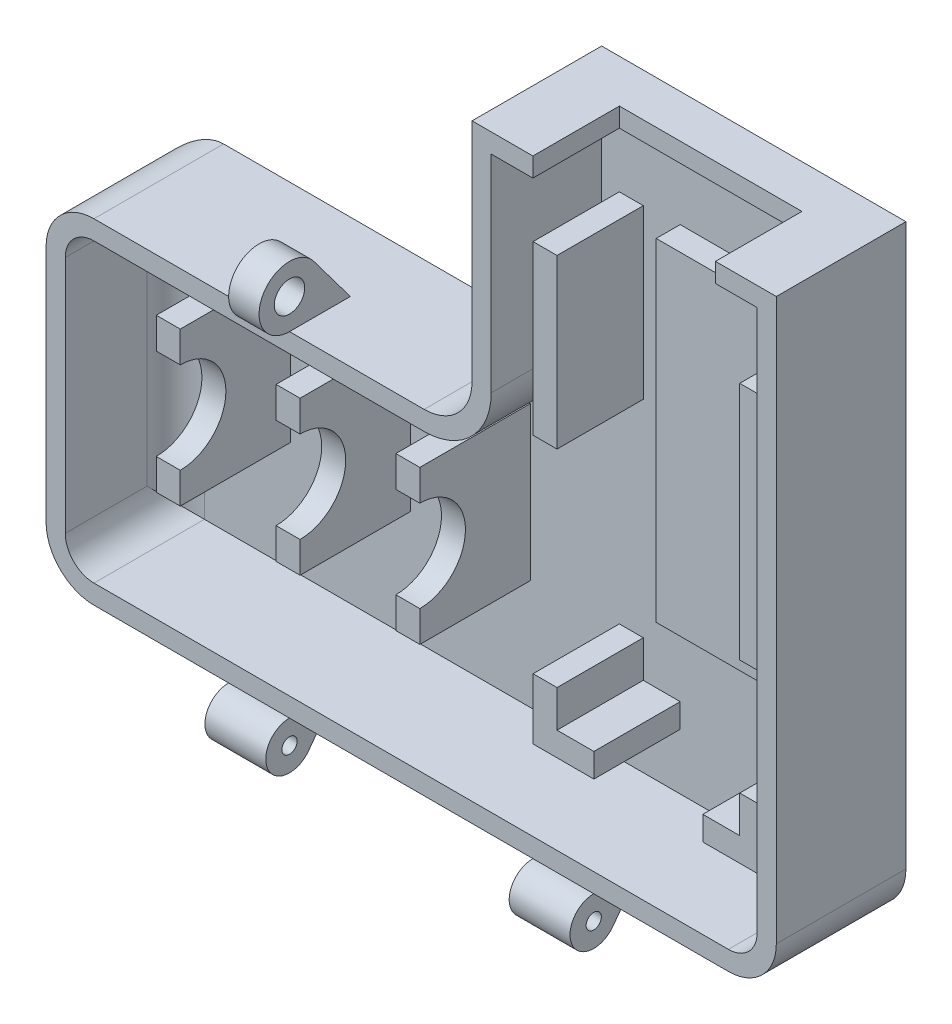
SolidWorks part; units mm, degrees
material "PET"
ref_plane "Alzado" through (0, 0, 0) normal (0, 0, 1) x (1, 0, 0)
ref_plane "Planta" through (0, 0, 0) normal (0, 1, 0) x (1, 0, 0)
ref_plane "Vista lateral" through (0, 0, 0) normal (1, 0, 0) x (0, 0, -1)
sketch "Croquis1" plane through (0, 0, 0) normal (0, 0, 1) x (1, 0, 0)
  line L0 (0, 0) -> (0, 127)
  line L1 (0, 127) -> (63.5, 127)
  line L2 (63.5, 69.85) -> (152.4, 69.85)
  line L3 (152.4, 0) -> (0, 0)
  line L4 (63.5, 69.85) -> (63.5, 127)
  line L5 (152.4, 69.85) -> (152.4, 0)
  dimension "D1" = 63.5
  dimension "D2" = 152.4
  dimension "D3" = 127
  dimension "D4" = 57.15
extrude "Saliente-Extruir1" add sketch "Croquis1" along normal blind 54.1
fillet "Redondeo1" radius 10 5 edges at (152.4, 34.925, 0) (0, 0, 27.05) (152.4, 0, 27.05) (152.4, 69.85, 27.05) (63.5, 69.85, 27.05)
sketch "Croquis2" plane through (152.4, 0, 0) normal (1, 0, 0) x (0, 0, -1)
  line L0 (0, 0) -> (-54.1, 0) construction
  line L1 (-54.1, 127) -> (-27.05, 127)
  line L2 (-54.1, 127) -> (-54.1, 0)
  line L3 (-54.1, 0) -> (-27.05, 0)
  line L4 (-27.05, 127) -> (-27.05, 0)
extrude "Cortar-Extruir1" cut sketch "Croquis2" against normal through all
shell "Vaciado1" thickness 4 removed face at (80.01, 54.9258, 27.05)
sketch "Croquis3" plane through (0, 0, 4) normal (0, 0, 1) x (1, 0, 0)
  line L0 (12.6847, 20.6881) -> (50.8153, 20.6881)
  line L1 (50.8153, 20.6881) -> (50.8153, 33.3881)
  line L2 (50.8153, 33.3881) -> (139.7153, 33.3881)
  line L3 (139.7153, 33.3881) -> (139.7153, 52.4381)
  line L4 (139.7153, 52.4381) -> (50.8153, 52.4381)
  line L5 (50.8153, 52.4381) -> (50.8153, 122.2881)
  line L6 (50.8153, 122.2881) -> (12.6847, 122.2881)
  line L7 (12.6847, 122.2881) -> (12.6847, 20.6881)
  line L8 (12.6847, 28.3881) -> (7.6847, 28.3881)
  line L9 (7.6847, 28.3881) -> (7.6847, 15.6881)
  line L10 (7.6847, 15.6881) -> (20.3847, 15.6881)
  line L11 (20.3847, 15.6881) -> (20.3847, 20.6881)
  line L12 (50.8153, 28.3881) -> (55.8153, 28.3881)
  line L13 (55.8153, 28.3881) -> (55.8153, 15.6881)
  line L14 (55.8153, 15.6881) -> (43.1153, 15.6881)
  line L15 (43.1153, 15.6881) -> (43.1153, 20.6881)
  line L16 (7.6847, 52.4381) -> (12.6847, 52.4381)
  line L17 (7.6847, 52.4381) -> (7.6847, 102.4381)
  line L18 (7.6847, 102.4381) -> (12.6847, 102.4381)
  line L19 (12.6847, 52.4381) -> (12.6847, 102.4381)
  line L20 (50.8153, 106.4881) -> (55.8153, 106.4881)
  line L21 (50.8153, 106.4881) -> (50.8153, 71.4881)
  line L22 (50.8153, 71.4881) -> (55.8153, 71.4881)
  line L23 (55.8153, 106.4881) -> (55.8153, 71.4881)
  line L24 (20.3847, 106.9132) -> (43.1153, 106.9132)
  line L25 (20.3847, 106.9132) -> (20.3847, 37.5203)
  line L26 (20.3847, 37.5203) -> (43.1153, 37.5203)
  line L27 (43.1153, 106.9132) -> (43.1153, 37.5203)
  line L28 (4, 123) -> (59.5, 123) construction
  point P30 (31.75, 122.2881)
  point P33 (31.75, 123)
  point P34 (31.75, 106.9132)
  dimension "D1" = 101.6
  dimension "D2" = 12.7
  dimension "D3" = 12.7
  dimension "D4" = 5
  dimension "D5" = 5
  dimension "D6" = 5
  dimension "D7" = 50
  dimension "D8" = 35
  dimension "D9" = 38.1306
extrude "Saliente-Extruir2" add sketch "Croquis3" along normal blind 5 contours L27 L24 L25 L26 region at (31.75, 72.2168, 4)
extrude "Saliente-Extruir3" add sketch "Croquis3<3>" along normal blind 18 contours L18 L17 L16 L7 | L23 L20 L5 L22 | L15 L14 L13 L12 L1 L0 | L10 L11 L0 L7 L8 L9 region at (12.5815, 20.5849, 4) region at (50.9185, 20.5849, 4) region at (10.1847, 77.4381, 4) region at (53.3153, 88.9881, 4)
sketch "Croquis3<3>" plane through (0, 0, 4) normal (0, 0, 1) x (1, 0, 0) same geometry as "Croquis3"
sketch "Croquis4" plane through (0, 0, 4) normal (0, 0, 1) x (1, 0, 0)
  line L0 (139.7153, 33.3881) -> (139.7153, 52.4381) construction
  line L1 (74.4, 58.9132) -> (79.4, 58.9132)
  line L2 (74.4, 58.9132) -> (74.4, 26.9131)
  line L3 (74.4, 26.9131) -> (79.4, 26.9131)
  line L4 (79.4, 58.9132) -> (79.4, 26.9131)
  line L5 (99.4, 58.9132) -> (104.4, 58.9132)
  line L6 (99.4, 58.9132) -> (99.4, 26.9131)
  line L7 (99.4, 26.9131) -> (104.4, 26.9131)
  line L8 (104.4, 58.9132) -> (104.4, 26.9131)
  line L9 (124.4, 58.9132) -> (129.4, 58.9132)
  line L10 (124.4, 58.9132) -> (124.4, 26.9131)
  line L11 (124.4, 26.9131) -> (129.4, 26.9131)
  line L12 (129.4, 58.9132) -> (129.4, 26.9131)
  line L13 (152.4, 10) -> (152.4, 59.85) construction
  point P12 (129.4, 42.9131)
  point P15 (139.7153, 42.9131)
  point P16 (104.4, 42.9131)
  point P17 (79.4, 42.9131)
  dimension "D1" = 5
  dimension "D2" = 23
  dimension "D3" = 20
  dimension "D4" = 20
  dimension "D5" = 32.0001
extrude "Saliente-Extruir4" add sketch "Croquis4" along normal up to surface (23.05 mm away) up to face at (80.01, 54.9258, 27.05)
sketch "Croquis5" plane through (129.4, 0, 0) normal (1, 0, 0) x (0, 0, -1)
  line L0 (-27.05, 58.9132) -> (-27.05, 26.9131) construction
  circle A0 centre (-27.05, 42.9131) radius 9.525
  dimension "D1" = 19.05
extrude "Cortar-Extruir2" cut sketch "Croquis5" against normal up to surface (73.5847 mm away) up to face at (55.8153, 22.0381, 13)
sketch "Croquis6" plane through (0, 123, 0) normal (0, -1, 0) x (1, 0, 0)
  line L0 (59.5, 4) -> (4, 4) construction
  line L1 (12.7, 9) -> (50.8, 9)
  line L2 (12.7, 9) -> (12.7, 51.2778)
  line L3 (12.7, 51.2778) -> (50.8, 51.2778)
  line L4 (50.8, 9) -> (50.8, 51.2778)
  point P6 (31.75, 4)
  point P7 (31.75, 9)
  dimension "D1" = 5
  dimension "D2" = 38.1
extrude "Cortar-Extruir3" cut sketch "Croquis6" against normal blind 18
mirror "Simetría5" about plane through (0, 0, 54.1) normal (1, 0, 0) of bodies 107
sketch "Croquis7" plane through (0, 0, 27.05) normal (0, 0, 1) x (1, 0, 0)
  line L0 (-12.7, 127) -> (12.7, 127) construction
  line L1 (0, 127) -> (180.2409, 127)
  line L2 (0, 127) -> (0, -21.8751)
  line L3 (0, -21.8751) -> (180.2409, -21.8751)
  line L4 (180.2409, 127) -> (180.2409, -21.8751)
extrude "Cortar-Extruir4" cut sketch "Croquis7" against normal through all
ref_plane "Plano1" through (-38.1, 0, 0) normal (1, 0, 0) x (0, 0, -1)
sketch "Croquis8" plane through (-38.1, 0, 0) normal (1, 0, 0) x (0, 0, -1)
  line L0 (-27.05, 0) -> (0, 0) construction
  line L1 (-27.05, 0) -> (-17.144, 0)
  line L2 (-17.144, 0) -> (-23.0876, -7.9248)
  arc A0 (-27.05, 0) -> (-23.0876, -7.9248) centre (-27.05, -4.953) ccw
  dimension "D1" = 9.906
  dimension "D2" = 9.906
extrude "Saliente-Extruir5" add sketch "Croquis8" against normal blind 12.7
sketch "Croquis9" plane through (-38.1, 0, 0) normal (1, 0, 0) x (0, 0, -1)
  circle A0 centre (-27.05, -4.953) radius 1.5875
  dimension "D1" = 3.175
extrude "Cortar-Extruir5" cut sketch "Croquis9" against normal through all
ref_plane "Plano3" through (-76.2, 0, 0) normal (1, 0, 0) x (0, 0, -1)
mirror "Simetría6" about plane through (-76.2, 0, 0) normal (1, 0, 0) of "Cortar-Extruir5", "Saliente-Extruir5"
ref_plane "Plano4" through (-107.95, 0, 0) normal (-1, 0, 0) x (0, 0, 1)
sketch "Croquis10" plane through (-107.95, 0, 0) normal (-1, 0, 0) x (0, 0, 1)
  line L0 (27.05, 59.85) -> (27.05, 69.85) construction
  line L1 (0, 69.85) -> (27.05, 69.85) construction
  line L2 (27.05, 69.85) -> (14.35, 69.85)
  line L3 (14.35, 69.85) -> (21.97, 80.01)
  arc A0 (27.05, 69.85) -> (21.97, 80.01) centre (27.05, 76.2) ccw
  circle A1 centre (27.05, 76.2) radius 3.175
  dimension "D2" = 12.7
  dimension "D3" = 6.35
  dimension "D1" = 12.7
extrude "Saliente-Extruir6" add sketch "Croquis10" against normal blind 6.35
